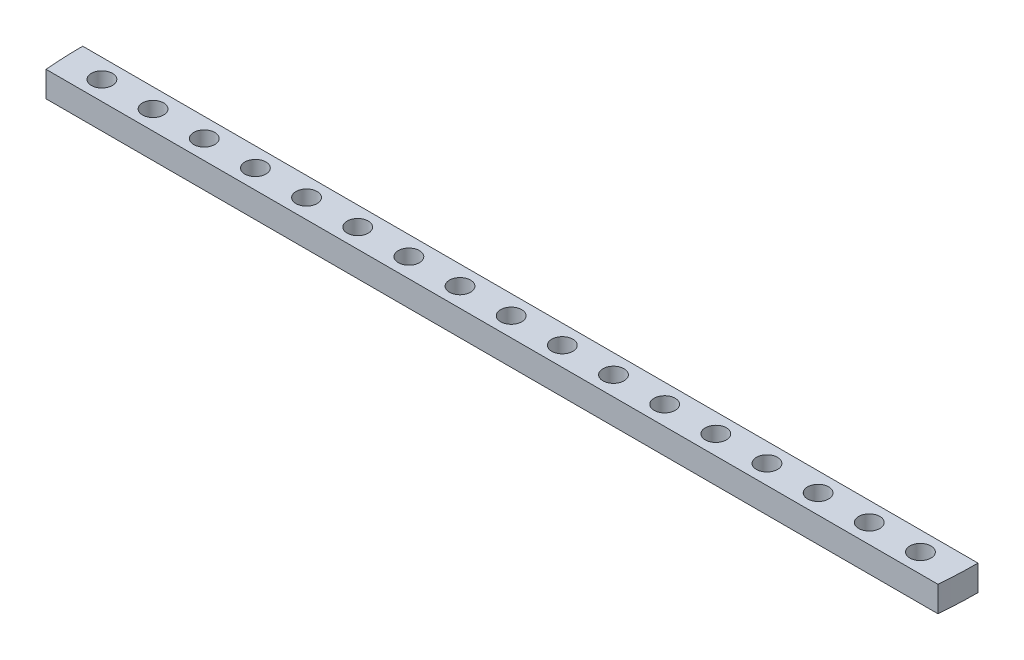
SolidWorks part; units mm, degrees
ref_plane "前视基准面" through (0, 0, 0) normal (0, 0, 1) x (1, 0, 0)
ref_plane "上视基准面" through (0, 0, 0) normal (0, 1, 0) x (1, 0, 0)
ref_plane "右视基准面" through (0, 0, 0) normal (1, 0, 0) x (0, 0, -1)
sketch "草图1" plane through (0, 0, 0) normal (0, 1, 0) x (1, 0, 0)
  line L0 (-50, 0) -> (50, 0)
  arc A0 (50, 0) -> (-50, 0) centre (0, 0) cw
extrude "凸台-拉伸1" add sketch "草图1" along normal blind 4
sketch "草图2" plane through (0, 4, 0) normal (0, 1, 0) x (1, 0, 0)
  line L2 (0, -10.623) -> (10, -10.623)
  line L3 (10, -10.623) -> (10, -30.623)
  line L4 (10, -30.623) -> (-30, -30.623)
  line L5 (-30, -30.623) -> (-30, -10.623)
  line L6 (-30, -10.623) -> (0, -10.623)
extrude "切除-拉伸1" cut sketch "草图2" against normal blind 10
sketch "草图3" plane through (0, 4, 0) normal (0, 1, 0) x (1, 0, 0)
  circle A0 centre (-34.75, -15.623) radius 2.25
  circle A1 centre (-34.75, -25.623) radius 2.25
  circle A2 centre (14.75, -25.623) radius 2.25
  circle A3 centre (14.75, -15.623) radius 2.25
extrude "切除-拉伸2" cut sketch "草图3" against normal blind 10
sketch "草图4" plane through (0, 4, 0) normal (0, 1, 0) x (1, 0, 0)
  circle A0 centre (0, -3) radius 1.65
  circle A1 centre (8, -3) radius 1.65
  circle A2 centre (16, -3) radius 1.65
  circle A3 centre (24, -3) radius 1.65
  circle A4 centre (32, -3) radius 1.65
  circle A5 centre (40, -3) radius 1.65
  circle A6 centre (-40, -3) radius 1.65
  circle A7 centre (-32, -3) radius 1.65
  circle A8 centre (-24, -3) radius 1.65
  circle A9 centre (-16, -3) radius 1.65
  circle A10 centre (-8, -3) radius 1.65
extrude "切除-拉伸3" cut sketch "草图4" against normal blind 10
sketch "草图5" plane through (0, 4, 0) normal (0, 1, 0) x (1, 0, 0)
  line L0 (-70, 0) -> (70, 0)
  circle A0 centre (0, 0) radius 70
  circle A1 centre (0, 0) radius 50
  arc M20 (-50, 0) -> (50, 0) centre (0, 0) ccw
extrude "凸台-拉伸2" add sketch "草图5" against normal blind 4 contours L0 A0 M20 region at (-60, 4, 1.5652)
sketch "草图6" plane through (0, 4, 0) normal (0, 1, 0) x (1, 0, 0)
  circle A0 centre (0, -3) radius 1.65
  circle A1 centre (8, -3) radius 1.65
  circle A2 centre (16, -3) radius 1.65
  circle A3 centre (24, -3) radius 1.65
  circle A4 centre (32, -3) radius 1.65
  circle A5 centre (40, -3) radius 1.65
  circle A6 centre (48, -3) radius 1.65
  circle A7 centre (56, -3) radius 1.65
  circle A8 centre (64, -3) radius 1.65
  circle A9 centre (-8, -3) radius 1.65
  circle A10 centre (-16, -3) radius 1.65
  circle A11 centre (-24, -3) radius 1.65
  circle A12 centre (-32, -3) radius 1.65
  circle A13 centre (-40, -3) radius 1.65
  circle A14 centre (-48, -3) radius 1.65
  circle A15 centre (-56, -3) radius 1.65
  circle A16 centre (-64, -3) radius 1.65
  dimension "D1" = 9
  dimension "D2" = 8
extrude "切除-拉伸4" cut sketch "草图6" against normal blind 4
sketch "草图7" plane through (0, 4, 0) normal (0, 1, 0) x (1, 0, 0)
  line L1 (-30, -20.623) -> (-30, -30.623)
  line L2 (10, -20.623) -> (10, -30.623)
  line L3 (-30, -30.623) -> (10, -30.623)
  line L4 (-30, -10.623) -> (-30, -30.623) construction
  line L5 (10, -30.623) -> (10, -10.623) construction
  line L7 (-30, -20.623) -> (10, -20.623)
  line L8 (-30, -20.623) -> (-30, -40.623)
  line L9 (10, -20.623) -> (10, -40.623)
  line L10 (-30, -40.623) -> (10, -40.623)
  line L11 (-34.75, -15.623) -> (14.75, -15.623)
  line L12 (14.75, -15.623) -> (14.75, -25.623)
  line L13 (14.75, -25.623) -> (14.75, -35.623)
  line L14 (-34.75, -15.623) -> (-34.75, -25.623)
  line L15 (-34.75, -25.623) -> (-34.75, -35.623)
  circle A1 centre (-34.75, -35.623) radius 2.25
  circle A2 centre (14.75, -35.623) radius 2.25
  line M30 (10, -30.623) -> (-30, -30.623)
extrude "切除-拉伸5" cut sketch "草图7" against normal blind 4 contours A1 | L8 L10 L9 M30 | A2 region at (-10, 4, 35.623) region at (16.296, 4, 34.0771) region at (-33.204, 4, 34.0771)
sketch "草图8" plane through (0, 4, 0) normal (0, 1, 0) x (1, 0, 0)
  line L0 (-34.75, -15.623) -> (14.75, -15.623)
  line L1 (14.75, -15.623) -> (14.75, -25.623)
  line L2 (14.75, -25.623) -> (14.75, -20.623)
  line L3 (14.75, -20.623) -> (-41.5549, -20.623)
  line L4 (-41.5549, -20.623) -> (-41.5549, -8.5064)
  line L5 (-41.5549, -8.5064) -> (21.0409, -8.9873)
  line L6 (21.0409, -8.9873) -> (21.0409, -20.623)
  line L7 (21.0409, -20.623) -> (14.75, -20.623)
  line M3 (-30, -40.623) -> (-30, -10.623)
  line M4 (-30, -10.623) -> (10, -10.623)
  line M5 (10, -10.623) -> (10, -40.623)
  circle M24 centre (14.75, -15.623) radius 2.25
  circle M27 centre (-34.75, -15.623) radius 2.25
extrude "凸台-拉伸4" add sketch "草图8" against normal blind 4 contours M27 | L3 L0 M5 M3 | L1 L0 M24 | L0 L1 M24 | L0 M3 M5 M4 region at (-10, 4, 13.123) region at (-10, 4, 18.123) region at (-36.9364, 4, 15.623) region at (15.0683, 4, 15.3047) region at (13.7951, 4, 16.578)
sketch "草图9" plane through (0, 4, 0) normal (0, 1, 0) x (1, 0, 0)
  line L0 (0, -70) -> (0, -80)
  line L1 (0, -80) -> (-10, -80)
  line L2 (-10, -80) -> (10, -80)
  line L3 (80, -80) -> (77, -80)
  line L4 (80, -10) -> (80, -150)
  line L5 (-30, -20.623) -> (10, -20.623)
  line L6 (-30, -20.623) -> (-30, -40.623)
  line L7 (10, -20.623) -> (10, -40.623)
  line L8 (-30, -40.623) -> (10, -40.623)
  line L9 (59.377, -90) -> (39.377, -90)
  line L10 (59.377, -50) -> (59.377, -90)
  line L11 (59.377, -50) -> (39.377, -50)
  line L12 (39.377, -50) -> (39.377, -90)
  line L17 (-59.377, -70) -> (-39.377, -70)
  line L18 (-59.377, -110) -> (-59.377, -70)
  line L19 (-59.377, -110) -> (-39.377, -110)
  line L20 (-39.377, -110) -> (-39.377, -70)
  line L21 (-80, -10) -> (-80, -150)
  arc A1 (80, -10) -> (80, -150) centre (80, -80) ccw
  circle A2 centre (77, -80) radius 1.65
  circle A3 centre (77, -72) radius 1.65
  circle A4 centre (77, -64) radius 1.65
  circle A5 centre (77, -56) radius 1.65
  circle A6 centre (77, -48) radius 1.65
  circle A7 centre (77, -40) radius 1.65
  circle A8 centre (77, -32) radius 1.65
  circle A9 centre (77, -24) radius 1.65
  circle A10 centre (77, -16) radius 1.65
  circle A11 centre (77, -88) radius 1.65
  circle A12 centre (77, -96) radius 1.65
  circle A13 centre (77, -104) radius 1.65
  circle A14 centre (77, -112) radius 1.65
  circle A15 centre (77, -120) radius 1.65
  circle A16 centre (77, -128) radius 1.65
  circle A17 centre (77, -136) radius 1.65
  circle A18 centre (77, -144) radius 1.65
  circle A19 centre (14.75, -25.623) radius 2.25
  circle A20 centre (14.75, -35.623) radius 2.25
  circle A21 centre (-34.75, -25.623) radius 2.25
  circle A22 centre (-34.75, -35.623) radius 2.25
  circle A23 centre (44.377, -45.25) radius 2.25
  circle A24 centre (54.377, -45.25) radius 2.25
  circle A25 centre (54.377, -94.75) radius 2.25
  circle A26 centre (44.377, -94.75) radius 2.25
  circle A31 centre (-44.377, -114.75) radius 2.25
  circle A32 centre (-54.377, -114.75) radius 2.25
  circle A33 centre (-54.377, -65.25) radius 2.25
  circle A34 centre (-44.377, -65.25) radius 2.25
  circle A35 centre (-77, -144) radius 1.65
  circle A36 centre (-77, -136) radius 1.65
  circle A37 centre (-77, -128) radius 1.65
  circle A38 centre (-77, -120) radius 1.65
  circle A39 centre (-77, -112) radius 1.65
  circle A40 centre (-77, -104) radius 1.65
  circle A41 centre (-77, -96) radius 1.65
  circle A42 centre (-77, -88) radius 1.65
  circle A43 centre (-77, -80) radius 1.65
  circle A44 centre (-77, -72) radius 1.65
  circle A45 centre (-77, -64) radius 1.65
  circle A46 centre (-77, -56) radius 1.65
  circle A47 centre (-77, -48) radius 1.65
  circle A48 centre (-77, -40) radius 1.65
  circle A49 centre (-77, -32) radius 1.65
  circle A50 centre (-77, -24) radius 1.65
  circle A51 centre (-77, -16) radius 1.65
  arc A52 (-80, -10) -> (-80, -150) centre (-80, -80) cw
  point P61 (0, 0)
  point P62 (0, 0)
  point P63 (0, 0)
  point P100 (0, -80)
extrude "凸台-拉伸7" add sketch "草图9" against normal blind 4 contours A24 L9 L11 L10 L12 A1 L4 A2 A26 A25 A18 A17 A16 A15 A14 A13 A12 A11 A10 A9 A8 A7 A6 A5 A4 | A52 L21 L9 A50 A48 A46 A44 A42 A40 A38 A36 L20 L19 L18 L17 A31 A32 A33 A34 A35 A37 A39 A41 A43 A45 A47 A49 region at (-31.6093, 4, 128.3907) region at (31.6093, 4, 31.6093)
sketch "草图10" plane through (0, 4, 0) normal (0, 1, 0) x (1, 0, 0)
  line L0 (59.377, -50) -> (59.377, -90)
  line L1 (59.377, -50) -> (39.377, -50)
  line L2 (59.377, -90) -> (39.377, -90)
  line L3 (39.377, -50) -> (39.377, -90)
  circle A0 centre (54.377, -45.25) radius 2.25
  circle A1 centre (44.377, -45.25) radius 2.25
extrude "切除-拉伸6" cut sketch "草图10" against normal blind 4
sketch "草图11" plane through (0, 0, 0) normal (0, -1, 0) x (1, 0, 0)
  line L0 (0, 0) -> (0, 6)
  line L1 (0, 6) -> (-85.0456, 6)
  line L2 (-85.0456, 6) -> (-85.0456, 166.3409)
  line L3 (-85.0456, 166.3409) -> (96.12, 166.3409)
  line L4 (96.12, 166.3409) -> (96.12, 6)
  line L5 (96.12, 6) -> (0, 6)
  circle A0 centre (0, 0) radius 70
extrude "切除-拉伸7" cut sketch "草图11" against normal blind 4 contours A0 L5 L4 L3 L2 L1 | L5 A0 L1 region at (0, 0, 32.9766) region at (7.2485, 0, 102.61)
